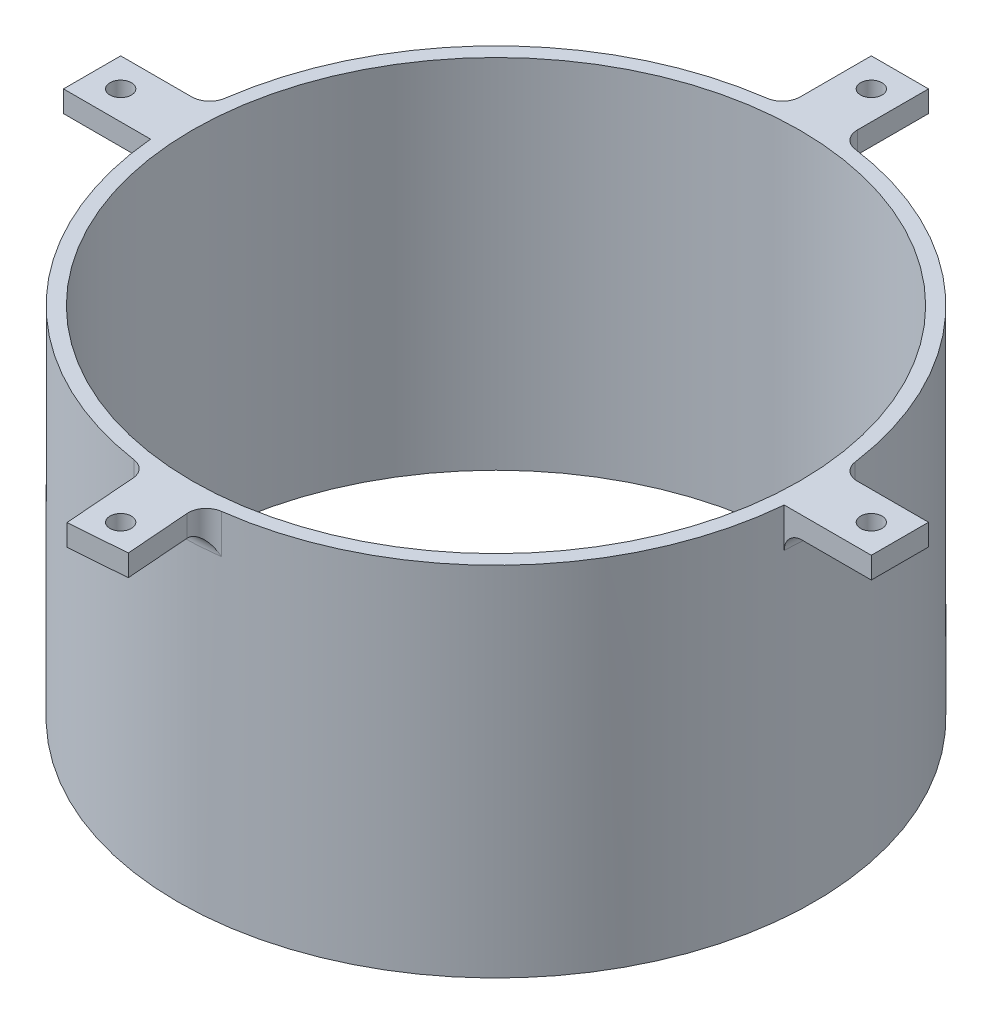
SolidWorks part; units mm, degrees
ref_plane "Front Plane" through (0, 0, 0) normal (0, 0, 1) x (1, 0, 0)
ref_plane "Top Plane" through (0, 0, 0) normal (0, 1, 0) x (1, 0, 0)
ref_plane "Right Plane" through (0, 0, 0) normal (1, 0, 0) x (0, 0, -1)
sketch "Sketch1" plane through (0, 0, 0) normal (0, 1, 0) x (1, 0, 0)
  circle A0 centre (0, 0) radius 85
  circle A1 centre (0, 0) radius 89
  arc A2 (-85, 0) -> (85, 0) centre (0, 0) cw construction
  arc A3 (-89, 0) -> (89, 0) centre (0, 0) cw construction
  point P7 (7.5797, -84.6614)
  point P9 (-85, 1.9576)
  point P10 (-73.3731, -50.3725)
  point P12 (89, -2.3845)
  dimension "D1" = 85
  dimension "D2" = 4
extrude "Boss-Extrude1" add sketch "Sketch1" along normal blind 100
sketch "Sketch2" plane through (0, 100, 0) normal (0, 1, 0) x (1, 0, 0)
  line L0 (8, 88.6397) -> (8, 113)
  line L1 (8, 113) -> (-8, 113)
  line L2 (-8, 113) -> (-8, 88.6397)
  line L3 (0, 0) -> (0, 105) construction
  line L4 (-113, 8) -> (-88.6397, 8)
  line L5 (-113, 8) -> (-113, -8)
  line L6 (-113, -8) -> (-88.6397, -8)
  line L8 (113, 8) -> (88.6397, 8)
  line L9 (113, 8) -> (113, -8)
  line L10 (113, -8) -> (85, -8)
  line L15 (88.6397, 8) -> (85, 8.9224)
  line L16 (85, 8.9224) -> (85, -8)
  line L17 (-88.6397, -8) -> (-85.6239, -8)
  line L18 (-85.6239, -8) -> (-85.6239, 8)
  line L19 (-85.6239, 8) -> (-88.6397, 8)
  line L20 (8, 88.6397) -> (8, 86.3334)
  line L21 (8, 86.3334) -> (-8, 86.3334)
  line L22 (-8, 86.3334) -> (-8, 88.6397)
  line L23 (6.6683, -87.267) -> (8.5101, -111.3701)
  line L24 (8.5101, -111.3701) -> (-7.4434, -112.5892)
  line L25 (-7.4434, -112.5892) -> (-9.3783, -87.267)
  line L26 (-9.3783, -87.267) -> (6.6683, -87.267)
  circle A1 centre (0, 0) radius 105 construction
  circle A2 centre (0, 105) radius 3
  circle A3 centre (-105, 0) radius 3
  circle A4 centre (105, 0) radius 3
  circle A5 centre (0, 0) radius 89 construction
  circle A6 centre (0, -105) radius 3
  circle A7 centre (0, 0) radius 89 construction
  circle M3 centre (0, 0) radius 89
  dimension "D1" = 210
  dimension "D2" = 6
  dimension "D3" = 6
  dimension "D4" = 6
  dimension "D14" = 6
  dimension "D5" = 8
  dimension "D6" = 8
  dimension "D7" = 8
  dimension "D8" = 8
  dimension "D9" = 8
  dimension "D10" = 8
  dimension "D11" = 8
  dimension "D12" = 8
  dimension "D13" = 8
  dimension "D15" = 8
  dimension "D16" = 8
  dimension "D17" = 7
extrude "Boss-Extrude2" add sketch "Sketch2" against normal blind 6 contours L10 L9 L8 A4 M3 | L1 L2 L0 A2 M3 | L4 L5 L6 A3 M3 | L25 L24 L23 A6 M3 region at (0, 100, -100.6188) region at (100.6188, 100, 0) region at (-100.6188, 100, 0) region at (-0.4687, 100, 100.05)
fillet "Fillet1" radius 5 10 edges at (-89, 94, 0) (-88.6397, 97, -8) (89, 94, 0) (88.6397, 97, -8) (-8, 97, -88.6397) (8, 97, -88.6397) (0, 94, -89) (6.781, 97, 88.7413) (-1.2562, 94, 88.9911) (-9.283, 97, 88.5146)
